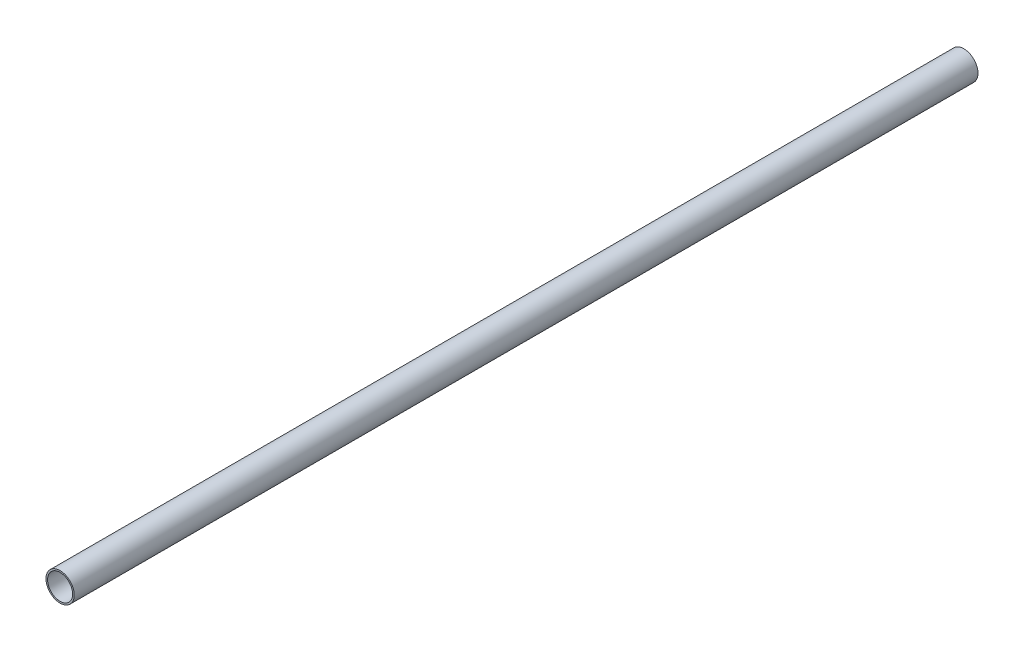
SolidWorks part; units mm, degrees
material "AISI 4130 Steel, normalized at 870C"
ref_plane "X-Y Datum" through (0, 0, 0) normal (0, 0, 1) x (1, 0, 0)
ref_plane "X-Z Datum" through (0, 0, 0) normal (0, 1, 0) x (1, 0, 0)
ref_plane "Y-Z Datum" through (0, 0, 0) normal (1, 0, 0) x (0, 0, -1)
sketch "Sketch - Tube cross section" plane through (0, 0, 0) normal (0, 0, 1) x (1, 0, 0)
  circle A0 centre (0, 0) radius 7.9375
  circle A1 centre (0, 0) radius 7.0485
  point P0 (0, 0)
  dimension "D1" = 15.875
  dimension "D2" = 0.889
extrude "Extrude - Tube body" add sketch "Sketch - Tube cross section" along normal blind 254 and the other way blind 254
equation "\"torsion bar OD\"= 0.625in"
equation "\"torsion bar wall thickness\"= 0.035in"
equation "\"torsion bar total length\"= 20in"
equation "\"D1@Sketch - Tube cross section\"=\"torsion bar OD\""
equation "\"D2@Sketch - Tube cross section\"=\"torsion bar wall thickness\""
equation "\"D1@Extrude - Tube body\" = \"torsion bar total length\" / 2"
equation "\"D2@Extrude - Tube body\"=\"torsion bar total length\"/2"
